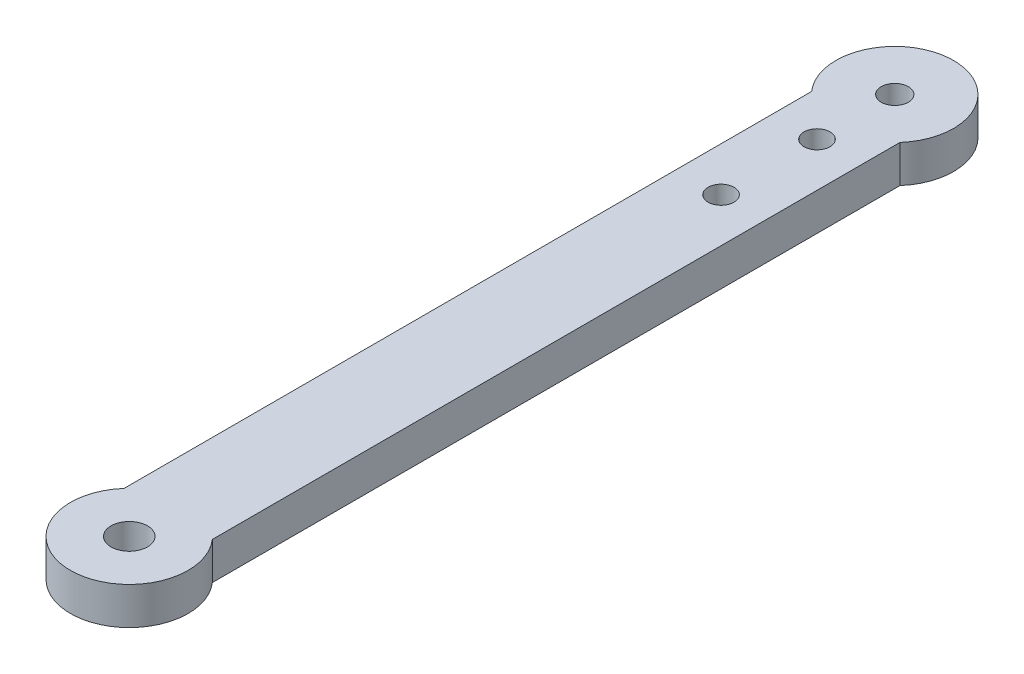
SolidWorks part; units mm, degrees
ref_plane "Front Plane" through (0, 0, 0) normal (0, 0, 1) x (1, 0, 0)
ref_plane "Top Plane" through (0, 0, 0) normal (0, 1, 0) x (1, 0, 0)
ref_plane "Right Plane" through (0, 0, 0) normal (1, 0, 0) x (0, 0, -1)
sketch "Sketch1" plane through (0, 0, 0) normal (0, 1, 0) x (1, 0, 0)
  line L1 (-3.75, -61.6928) -> (-3.75, -3.3072)
  line L4 (3.75, -61.6928) -> (3.75, -3.3072)
  line L5 (-3.75, -3.3072) -> (0, 0) construction
  line L6 (0, 0) -> (3.75, -3.3072) construction
  line L7 (-3.75, -3.3072) -> (3.75, -3.3072) construction
  arc A1 (3.75, -3.3072) -> (-3.75, -3.3072) centre (0, 0) ccw
  arc A2 (-3.75, -61.6928) -> (3.75, -61.6928) centre (0, -65) ccw
  circle A3 centre (0, -65) radius 1.55
  circle A5 centre (0, -6.6) radius 1.1
  circle A6 centre (0, -14.75) radius 1.1
  circle A25 centre (0, 0) radius 1.15
  dimension "D2" = 2.2
  dimension "D3" = 10
  dimension "D6" = 10
  dimension "D5" = 3.1
  dimension "D8" = 2.3
  dimension "D1" = 8.15
  dimension "D4" = 7.5
  dimension "D7" = 65
  dimension "D9" = 6.6
extrude "Boss-Extrude1" add sketch "Sketch1" along normal blind 3.175
